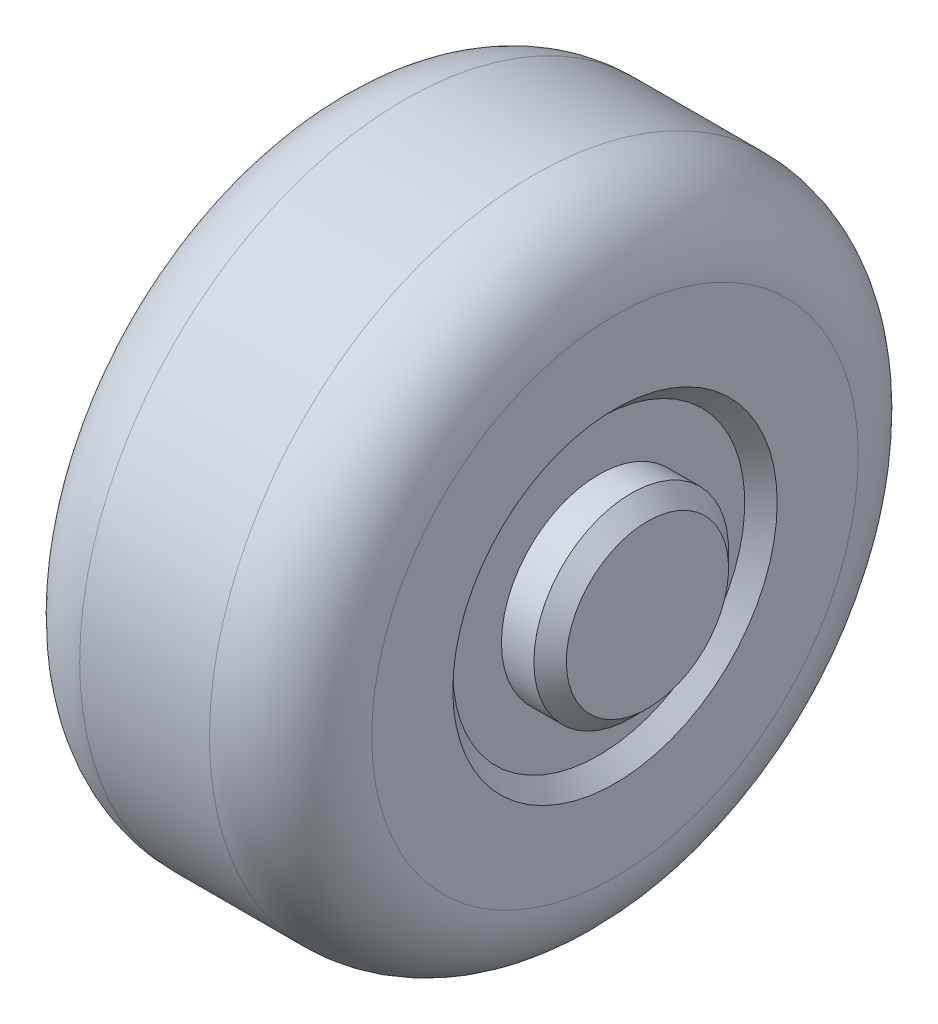
SolidWorks part; units mm, degrees
material "A6061"
ref_plane "前视基准面" through (0, 0, 0) normal (0, 0, 1) x (1, 0, 0)
ref_plane "上视基准面" through (0, 0, 0) normal (0, 1, 0) x (1, 0, 0)
ref_plane "右视基准面" through (0, 0, 0) normal (1, 0, 0) x (0, 0, -1)
sketch "草图1" plane through (0, 0, 0) normal (0, 0, 1) x (1, 0, 0)
  line L0 (-11, 0) -> (-11, 5)
  line L1 (-11, 5) -> (-10, 6)
  line L2 (-10, 6) -> (-8, 6)
  line L3 (-8, 6) -> (-8, 9)
  line L4 (-8, 9) -> (-9, 10)
  line L5 (-9, 10) -> (-9, 15)
  line L6 (-4, 20) -> (4, 20)
  line L7 (9, 15) -> (9, 10)
  line L8 (9, 10) -> (8, 9)
  line L9 (8, 9) -> (8, 6)
  line L10 (8, 6) -> (10, 6)
  line L11 (10, 6) -> (11, 5)
  line L12 (11, 5) -> (11, 0)
  line L13 (11, 0) -> (-11, 0)
  line L14 (11, 0) -> (-11, 0) construction
  arc A0 (-9, 15) -> (-4, 20) centre (-4, 15) cw
  arc A1 (4, 20) -> (9, 15) centre (4, 15) cw
revolve "旋转1" add sketch "草图1" angle 360 about L14 reverse direction yes
ref_plane "wheel_to_body XY" through (0, 0, 0) normal (1, 0, 0) x (0, 0, -1)
ref_plane "wheel_to_body XZ" through (0, 0, 0) normal (0, -1, 0) x (-1, 0, 0)
ref_plane "wheel_to_body YZ" through (0, 0, 0) normal (0, 0, -1) x (-1, 0, 0)
ref_axis "wheel_to_body X" through (0, 0, 80.9) along (0, 0, -1)
ref_axis "wheel_to_body Y" through (0, -50, 0) along (0, 1, 0)
ref_axis "wheel_to_body Z" through (80.9, 0, 0) along (-1, 0, 0)
sketch3d "wheel_to_body"
  point P0 (0, 0, 0)
